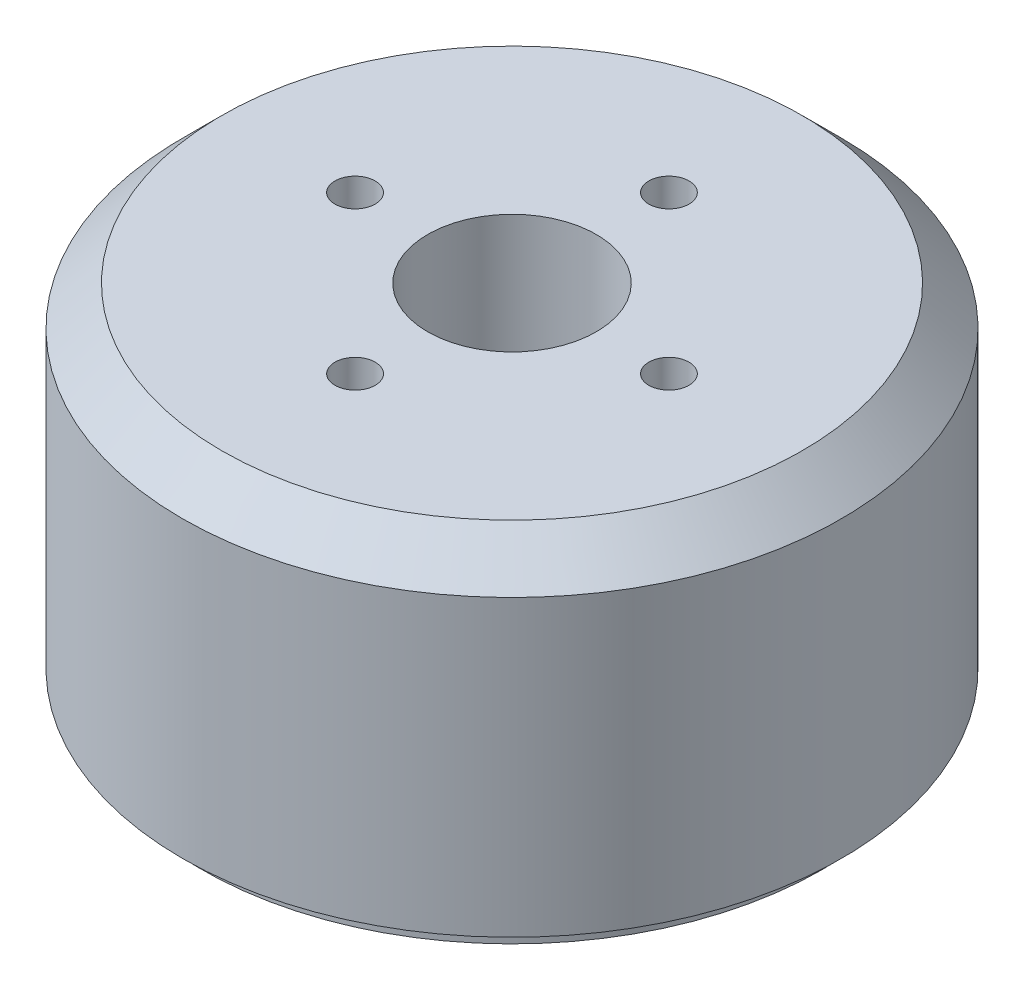
SolidWorks part; units mm, degrees
material "自定义塑料"
ref_plane "前视基准面" through (0, 0, 0) normal (0, 0, 1) x (1, 0, 0)
ref_plane "上视基准面" through (0, 0, 0) normal (0, 1, 0) x (1, 0, 0)
ref_plane "右视基准面" through (0, 0, 0) normal (1, 0, 0) x (0, 0, -1)
sketch "草图2" plane through (0, 0, 0) normal (0, 1, 0) x (1, 0, 0)
  circle A0 centre (0, 0) radius 16.8
  dimension "D1" = 33.6
extrude "凸台-拉伸1" add sketch "草图2" along normal blind 18 contours A0
sketch "草图4" plane through (0, 18, 0) normal (0, 1, 0) x (1, 0, 0)
  circle A0 centre (0, 0) radius 4.3
  dimension "D1" = 8.6
extrude "切除-拉伸1" cut sketch "草图4" against normal through all
chamfer "倒角1" distance 2 angle 45 1 edges at (0, 18, 16.8)
ref_axis "基准轴1" through (0, 0, 0) along (0, 1, 0)
hole_wizard "M2.5 螺纹孔1" positions "草图5" profile "草图7" tap size "M2.5" standard "GB"
sketch "草图5" plane through (0, 18, 0) normal (0, 1, 0) x (1, 0, 0)
  line L1 (0, 0) -> (0, 8) construction
  point P0 (0, 8)
  dimension "D1" = 8
sketch "草图7" plane through (0, 18, -8) normal (1, 0, 0) x (0, 0, 1)
  line L0 (0, 0) -> (0, 4.6159)
  line L1 (0, 4.6159) -> (1.025, 4)
  line L2 (1.025, 4) -> (1.025, 0)
  line L5 (1.025, 0) -> (0, 0)
  line L10 (0, 4.6159) -> (-1.025, 4) construction
  line L11 (0, -6.35) -> (0, 107.95) construction
  dimension "螺纹孔钻头直径" = 2.05
  dimension "螺纹孔钻头深度" = 4
  dimension "导头角度" = 118
cosmetic thread "孔螺蚊线1" parameters "D1"=5, "D2"=2.5
pattern_circular "阵列(圆周)1" count 4 over 360 about axis through (0, 0, 0) along (0, 1, 0) of "M2.5 螺纹孔1"
cosmetic thread "孔螺蚊线2" parameters "D1"=5, "D2"=2.5
cosmetic thread "孔螺蚊线3" parameters "D1"=5, "D2"=2.5
cosmetic thread "孔螺蚊线4" parameters "D1"=5, "D2"=2.5
sketch "草图8" plane through (0, 0, 0) normal (0, -1, 0) x (1, 0, 0)
  circle A0 centre (0, 0) radius 4.3 construction
  circle A1 centre (0, 0) radius 4.3
extrude "拉伸-薄壁1" add sketch "草图8" along normal blind 2 thin thin type one direction wall 1
sketch "草图9" plane through (0, -2, 0) normal (0, -1, 0) x (1, 0, 0)
  circle A0 centre (0, 0) radius 5.3 construction
  circle A1 centre (0, 0) radius 5.3
extrude "切除-拉伸-薄壁1" cut sketch "草图9" against normal blind 0.5 thin thin type one direction reverse wall 0.5
sketch "草图10" plane through (0, 0, 0) normal (0, -1, 0) x (1, 0, 0)
  circle A0 centre (0, 0) radius 16.8 construction
  circle A1 centre (0, 0) radius 16.8
extrude "切除-拉伸-薄壁2" cut sketch "草图10" against normal blind 1 thin thin type one direction reverse wall 1
hole_wizard "M2.5 螺纹孔2" positions "草图11" profile "草图12" tap size "M2.5" standard "GB"
sketch "草图11" plane through (0, 0, 0) normal (0, -1, 0) x (-1, 0, 0)
  line L0 (0, 0) -> (-11, 0) construction
  point P0 (-11, 0)
  dimension "D1" = 11
sketch "草图12" plane through (11, 0, 0) normal (1, 0, 0) x (0, 0, -1)
  line L0 (0, 0) -> (0, 4.6159)
  line L1 (0, 4.6159) -> (1.025, 4)
  line L2 (1.025, 4) -> (1.025, 0)
  line L5 (1.025, 0) -> (0, 0)
  line L10 (0, 4.6159) -> (-1.025, 4) construction
  line L11 (0, -6.35) -> (0, 107.95) construction
  dimension "螺纹孔钻头直径" = 2.05
  dimension "螺纹孔钻头深度" = 4
  dimension "导头角度" = 118
cosmetic thread "孔螺蚊线5" parameters "D1"=5, "D2"=2.5
pattern_circular "阵列(圆周)2" count 4 over 360 about axis through (0, 0, 0) along (0, 1, 0) of "M2.5 螺纹孔2"
cosmetic thread "孔螺蚊线6" parameters "D1"=5, "D2"=2.5
cosmetic thread "孔螺蚊线7" parameters "D1"=5, "D2"=2.5
cosmetic thread "孔螺蚊线8" parameters "D1"=5, "D2"=2.5
